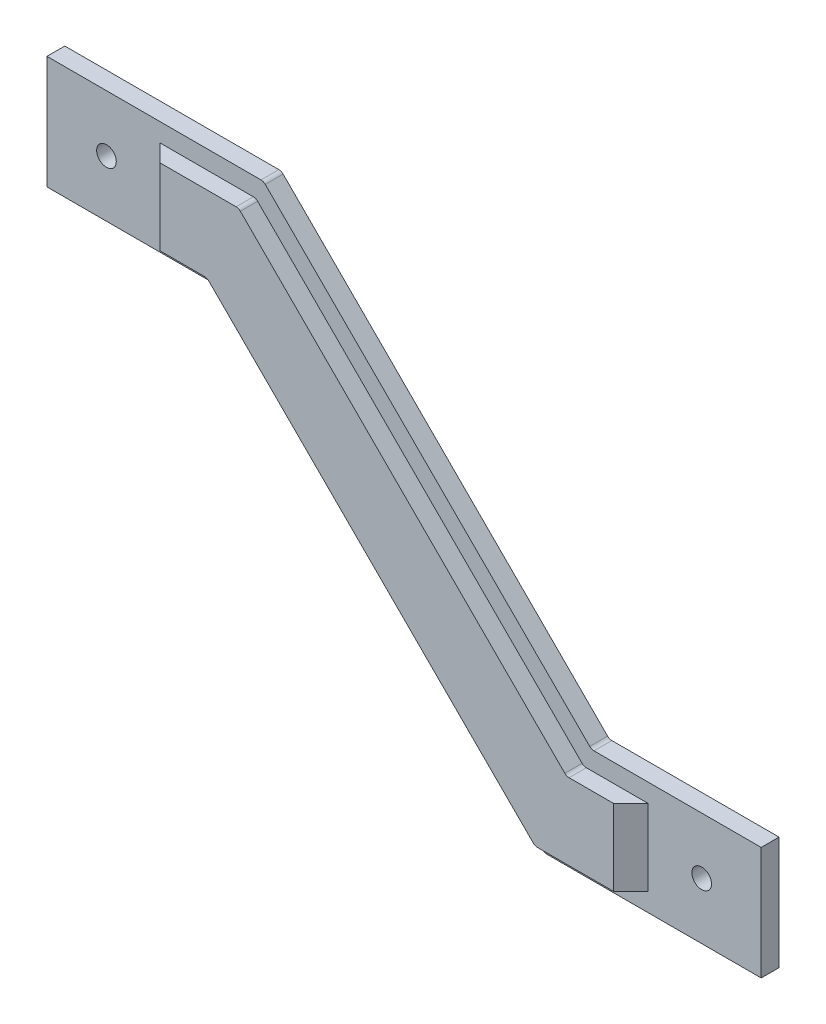
SolidWorks part; units mm, degrees
ref_plane "前视基准面" through (0, 0, 0) normal (0, 0, 1) x (1, 0, 0)
ref_plane "上视基准面" through (0, 0, 0) normal (0, 1, 0) x (1, 0, 0)
ref_plane "右视基准面" through (0, 0, 0) normal (1, 0, 0) x (0, 0, -1)
sketch "草图1" plane through (0, 0, 0) normal (0, 0, 1) x (1, 0, 0)
  line L0 (-60, 37.05) -> (-23.615, 37.05)
  line L1 (-23.615, 37.05) -> (31.485, -18.05)
  line L2 (31.485, -18.05) -> (60, -18.05)
  line L3 (60, -18.05) -> (60, -37.05)
  line L4 (60, -37.05) -> (23.615, -37.05)
  line L5 (23.615, -37.05) -> (-31.485, 18.05)
  line L6 (-31.485, 18.05) -> (-60, 18.05)
  line L7 (-60, 18.05) -> (-60, 37.05)
  line L8 (-23.615, 37.05) -> (23.615, -37.05) construction
  line L9 (-31.485, 18.05) -> (31.485, -18.05) construction
  circle A0 centre (-50, 27.55) radius 1.65
  circle A1 centre (50, -27.55) radius 1.65
  dimension "D2" = 3.3
  dimension "D1" = 19
  dimension "D3" = 100
  dimension "D4" = 55.1
  dimension "D5" = 9.5
  dimension "D6" = 9.5
  dimension "D7" = 135
  dimension "D8" = 19
  dimension "D9" = 10
  dimension "D10" = 10
extrude "凸台-拉伸1" add sketch "草图1" along normal blind 3
sketch "草图2" plane through (0, 0, 3) normal (0, 0, 1) x (1, 0, 0)
  line L0 (-41, 33.95) -> (-41, 21.15)
  line L1 (-41, 21.15) -> (-30.201, 21.15)
  line L2 (-30.201, 21.15) -> (24.899, -33.95)
  line L3 (24.899, -33.95) -> (41, -33.95)
  line L4 (41, -33.95) -> (41, -21.15)
  line L5 (41, -21.15) -> (30.201, -21.15)
  line L6 (30.201, -21.15) -> (-24.899, 33.95)
  line L7 (-24.899, 33.95) -> (-41, 33.95)
  line L8 (-23.615, 37.05) -> (-60, 37.05) construction
  line L9 (23.615, -37.05) -> (60, -37.05) construction
  line L10 (60, -37.05) -> (60, -18.05) construction
  line L11 (-60, 37.05) -> (-60, 18.05) construction
  line L12 (31.485, -18.05) -> (-23.615, 37.05) construction
  dimension "D1" = 12.8
  dimension "D2" = 12.8
  dimension "D3" = 3.1
  dimension "D4" = 3.1
  dimension "D5" = 19
  dimension "D6" = 19
  dimension "D7" = 12.8
extrude "凸台-拉伸2" add sketch "草图2" along normal blind 2.9
chamfer "倒角1" distance 2.9 angle 45 2 edges at (41, -27.55, 5.9) (-41, 27.55, 5.9)
fillet "圆角1" radius 1 8 edges at (-24.899, 33.95, 4.45) (-23.615, 37.05, 1.5) (31.485, -18.05, 1.5) (30.201, -21.15, 4.45) (23.615, -37.05, 1.5) (24.899, -33.95, 4.45) (-31.485, 18.05, 1.5) (-30.201, 21.15, 4.45)
